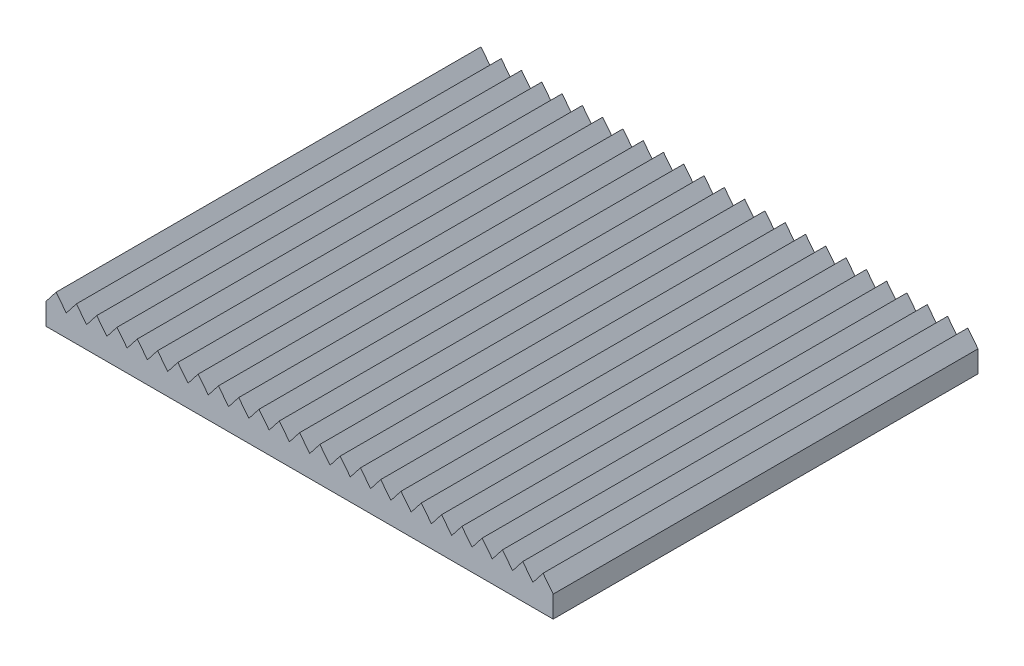
SolidWorks part; units mm, degrees
ref_plane "Front Plane" through (0, 0, 0) normal (0, 0, 1) x (1, 0, 0)
ref_plane "Top Plane" through (0, 0, 0) normal (0, 1, 0) x (1, 0, 0)
ref_plane "Right Plane" through (0, 0, 0) normal (1, 0, 0) x (0, 0, -1)
sketch "Sketch1" plane through (0, 0, 0) normal (0, 1, 0) x (1, 0, 0)
  line L6 (-29.25, 24.5) -> (29.25, 24.5)
  line L28 (-29.25, 24.5) -> (-29.25, -24.5)
  line L29 (-29.25, -24.5) -> (29.25, -24.5)
  line L30 (29.25, 24.5) -> (29.25, -24.5)
  line L31 (-29.25, 24.5) -> (29.25, -24.5) construction
  line L32 (-29.25, -24.5) -> (29.25, 24.5) construction
  circle A1 centre (0, 0) radius 3.1
  point P0 (0, 0)
  dimension "D3" = 6.2
  dimension "D1" = 58.5
  dimension "D2" = 49
extrude "Boss-Extrude1" add sketch "Sketch1" along normal blind 1.5
sketch "Sketch2" plane through (0, 0, -24.5) normal (0, 0, -1) x (-1, 0, 0)
  line L0 (-29.25, 1.5) -> (-29.25, 0) construction
  line L1 (-29.25, 1.5) -> (29.25, 1.5)
  line L2 (-29.25, 1.5) -> (-29.25, 2.5)
  line L4 (29.25, 1.5) -> (29.25, 2.5)
  line L5 (-1.17, 2.5) -> (0, 4)
  line L6 (0, 55) -> (0, -55) construction
  line L7 (1.17, 2.5) -> (0, 4)
  line L8 (1.17, 2.5) -> (2.34, 4)
  line L9 (3.51, 2.5) -> (2.34, 4)
  line L10 (3.51, 2.5) -> (4.68, 4)
  line L11 (5.85, 2.5) -> (4.68, 4)
  line L12 (5.85, 2.5) -> (7.02, 4)
  line L13 (8.19, 2.5) -> (7.02, 4)
  line L14 (8.19, 2.5) -> (9.36, 4)
  line L15 (10.53, 2.5) -> (9.36, 4)
  line L16 (10.53, 2.5) -> (11.7, 4)
  line L17 (12.87, 2.5) -> (11.7, 4)
  line L18 (12.87, 2.5) -> (14.04, 4)
  line L19 (15.21, 2.5) -> (14.04, 4)
  line L20 (15.21, 2.5) -> (16.38, 4)
  line L21 (17.55, 2.5) -> (16.38, 4)
  line L22 (17.55, 2.5) -> (18.72, 4)
  line L23 (19.89, 2.5) -> (18.72, 4)
  line L24 (19.89, 2.5) -> (21.06, 4)
  line L25 (22.23, 2.5) -> (21.06, 4)
  line L26 (22.23, 2.5) -> (23.4, 4)
  line L27 (24.57, 2.5) -> (23.4, 4)
  line L28 (24.57, 2.5) -> (25.74, 4)
  line L29 (26.91, 2.5) -> (25.74, 4)
  line L30 (26.91, 2.5) -> (28.08, 4)
  line L31 (29.25, 2.5) -> (28.08, 4)
  line L32 (-29.25, 2.5) -> (-28.08, 4)
  line L33 (-26.91, 2.5) -> (-28.08, 4)
  line L34 (-26.91, 2.5) -> (-25.74, 4)
  line L35 (-24.57, 2.5) -> (-25.74, 4)
  line L36 (-24.57, 2.5) -> (-23.4, 4)
  line L37 (-22.23, 2.5) -> (-23.4, 4)
  line L38 (-22.23, 2.5) -> (-21.06, 4)
  line L39 (-19.89, 2.5) -> (-21.06, 4)
  line L40 (-19.89, 2.5) -> (-18.72, 4)
  line L41 (-17.55, 2.5) -> (-18.72, 4)
  line L42 (-17.55, 2.5) -> (-16.38, 4)
  line L43 (-15.21, 2.5) -> (-16.38, 4)
  line L44 (-15.21, 2.5) -> (-14.04, 4)
  line L45 (-12.87, 2.5) -> (-14.04, 4)
  line L46 (-12.87, 2.5) -> (-11.7, 4)
  line L47 (-10.53, 2.5) -> (-11.7, 4)
  line L48 (-10.53, 2.5) -> (-9.36, 4)
  line L49 (-8.19, 2.5) -> (-9.36, 4)
  line L50 (-8.19, 2.5) -> (-7.02, 4)
  line L51 (-5.85, 2.5) -> (-7.02, 4)
  line L52 (-5.85, 2.5) -> (-4.68, 4)
  line L53 (-3.51, 2.5) -> (-4.68, 4)
  line L54 (-3.51, 2.5) -> (-2.34, 4)
  line L55 (-1.17, 2.5) -> (-2.34, 4)
  dimension "D1" = 1
  dimension "D2" = 1.5
  dimension "D3" = 13
extrude "Boss-Extrude2" add sketch "Sketch2" against normal blind 49
sketch "Sketch3" plane through (0, 0, 0) normal (0, -1, 0) x (-1, 0, 0)
  line L0 (0, 0.825) -> (0, -0.825) construction
  line L2 (-1.75, -2.5588) -> (-1.75, -5)
  line L3 (-1.75, -5) -> (1.75, -5)
  line L4 (1.75, -2.5588) -> (1.75, -5)
  arc A0 (1.75, -2.5588) -> (-1.75, -2.5588) centre (0, 0) ccw
  dimension "D2" = 6.2
  dimension "D1" = 3.5
  dimension "D3" = 5
  dimension "D4" = 1.75
extrude "Cut-Extrude1" cut sketch "Sketch3" against normal blind 2
chamfer "Chamfer1" distance 2 angle 45 1 edges at (0, 0, 5)
chamfer "Chamfer2" distance 0.2 angle 45 1 edges at (0, 0, -3.1)
